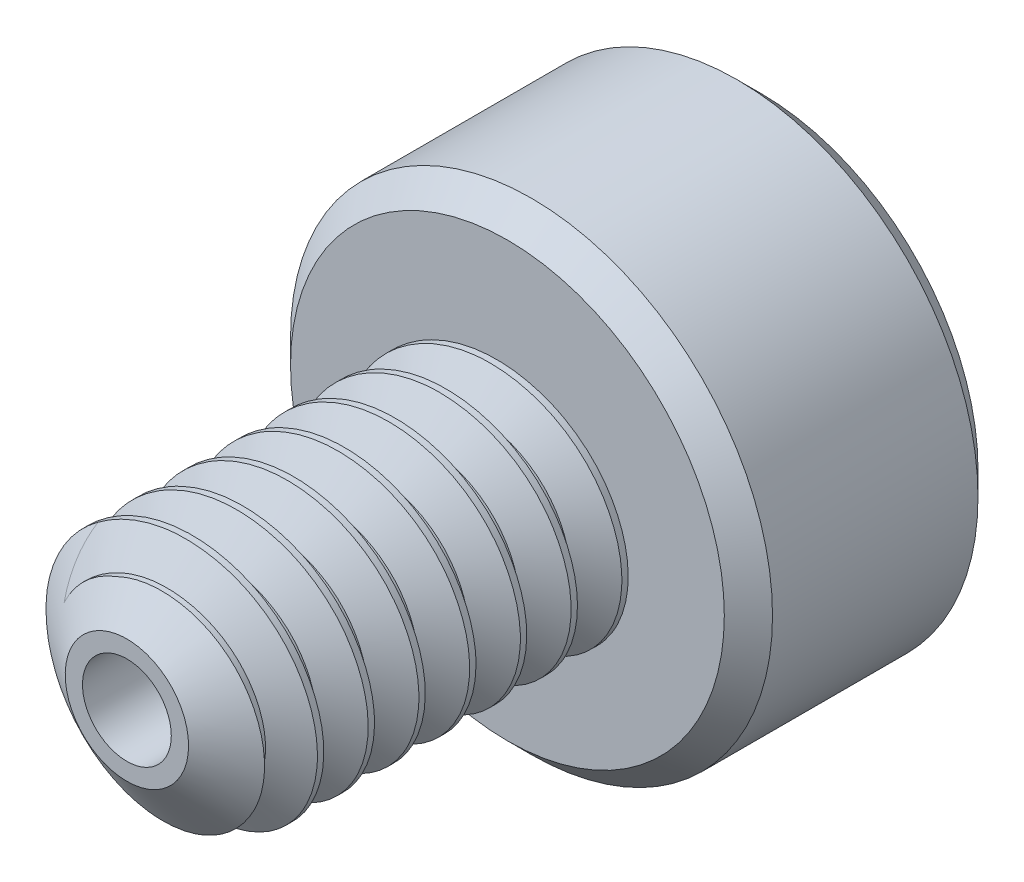
SolidWorks part; units mm, degrees
other "DetailItem1"
ref_plane "Front Plane" through (0, 0, 0) normal (0, 0, 1) x (1, 0, 0)
ref_plane "Top Plane" through (0, 0, 0) normal (0, 1, 0) x (1, 0, 0)
ref_plane "Right Plane" through (0, 0, 0) normal (1, 0, 0) x (0, 0, -1)
sketch "Sketch1" plane through (0, 0, 0) normal (0, 0, 1) x (1, 0, 0)
  circle A0 centre (0, 0) radius 1
  dimension "OD" = 2
extrude "Extrude1" add sketch "Sketch1" against normal blind 3
sketch "Sketch2" plane through (0, 0, 0) normal (0, 0, 1) x (1, 0, 0)
  circle A0 centre (0, 0) radius 1 construction
  circle A1 centre (0, 0) radius 1
curve "Helix/Spiral1" pitch 0.4 height 3.4 radius 1 centre (0, 0, 0) axis (0, 0, -1) start towards (0, 1, 0) parameters "pitch"=0.4
sketch "Sketch3" plane through (0, 0, 0) normal (1, 0, 0) x (0, 0, -1)
  line L0 (-0.35, 1) -> (-0.2, 0.7402)
  line L1 (-0.2, 0.7402) -> (-0.15, 0.7402)
  line L2 (-0.15, 0.7402) -> (0, 1)
  line L3 (-0.35, 1) -> (0, 1)
  line L4 (-0.175, 1) -> (-0.175, 0.7402) construction
  line L5 (-0.275, 0.8701) -> (-0.075, 0.8701) construction
  line L6 (0, 1) -> (0, -1) construction
  dimension "D1" = 0.05
  dimension "D2" = 0.2
  dimension "D3" = 60
sweep "Cut-Sweep1" cut profiles "Sketch3" path "Helix/Spiral1"
sketch "Sketch4" plane through (0, 0, 0) normal (1, 0, 0) x (0, 0, -1)
  line L0 (0.3598, 1) -> (0, 0.4862)
  line L1 (0, 0.4862) -> (0, 1)
  line L2 (0.3598, 1) -> (0, 1)
  line L3 (-0.35, 1) -> (0, 1) construction
  line L4 (0, 0) -> (7.0209, 0) construction
  dimension "D1" = 55
  dimension "D2" = 0.254
revolve "Cut-Revolve1" cut sketch "Sketch4" angle 360 about L4
sketch "Sketch6" plane through (0, 0, -3) normal (0, 0, -1) x (-1, 0, 0)
  circle A0 centre (0, 0) radius 1.9
  dimension "head dia" = 3.8
extrude "Extrude2" add sketch "Sketch6" along normal blind 2
sketch "Sketch7" plane through (0, 0, -5) normal (0, 0, -1) x (-1, 0, 0)
  line L1 (0, 0.866) -> (-0.75, 0.433)
  line L2 (-0.75, 0.433) -> (-0.75, -0.433)
  line L3 (-0.75, -0.433) -> (0, -0.866)
  line L4 (0, -0.866) -> (0.75, -0.433)
  line L5 (0.75, -0.433) -> (0.75, 0.433)
  line L6 (0.75, 0.433) -> (0, 0.866)
  circle A0 centre (0, 0) radius 0.75 construction
  dimension "hex dia" = 1.5
extrude "Cut-Extrude1" cut sketch "Sketch7" against normal blind 1.125
sketch "Sketch8" plane through (0, 0, -5) normal (0, 0, -1) x (-1, 0, 0)
  circle A0 centre (0, 0) radius 0.866
extrude "Cut-Extrude2" cut sketch "Sketch8" against normal through all draft 45
chamfer "Chamfer1" distance 0.19 angle 45 2 edges at (-1.9, 0, -5) (-1.9, 0, -3)
sketch "Sketch10" plane through (0, 0, -3) normal (0, 0, 1) x (1, 0, 0)
  circle A1 centre (0, 0) radius 1
  circle A2 centre (0, 0) radius 1
  dimension "D1" = 0
ref_plane "Plane1" through (0, 0, 0) normal (0, 0, 1) x (1, 0, 0)
extrude "partial thread" [suppressed] add sketch "Sketch10" along normal up to surface (12.7 mm away) separate body up to plane "Plane1"
chamfer "Chamfer2" [suppressed] distance 0.04 angle 45
combine bodies "Combine1" [suppressed] operation type add bodies to combine 107 108
sketch "Sketch9" plane through (0, 0, 0) normal (1, 0, 0) x (0, 0, -1)
  line L0 (0, 1) -> (0, -1) construction
  line L1 (1, 1) -> (1, -1) construction
  dimension "D1" = 1
sketch "Sketch11" plane through (0, 0, 0) normal (0, 0, 1) x (1, 0, 0)
  circle A0 centre (0, 0) radius 0.35
  dimension "Vent Dia" = 0.7
extrude "Cut-Extrude3" cut sketch "Sketch11" against normal through all
equation "\"D3@Helix/Spiral1\" = \"screw length@Extrude1\"+\"pitch@Helix/Spiral1\""
equation "\"D1@Sketch3\" = \"pitch@Helix/Spiral1\"*.125"
equation "\"D2@Sketch3\" = \"pitch@Helix/Spiral1\"*.5"
equation "\"D1@Cut-Extrude1\" = \"hex dia@Sketch7\"*.75"
equation "\"D1@Chamfer1\" = \"head dia@Sketch6\"*.05"
equation "\"D1@Sketch9\" = \"pitch@Helix/Spiral1\"*2.5"
equation "\"D1@Chamfer2\"=\"OD@Sketch1\"*.02"
